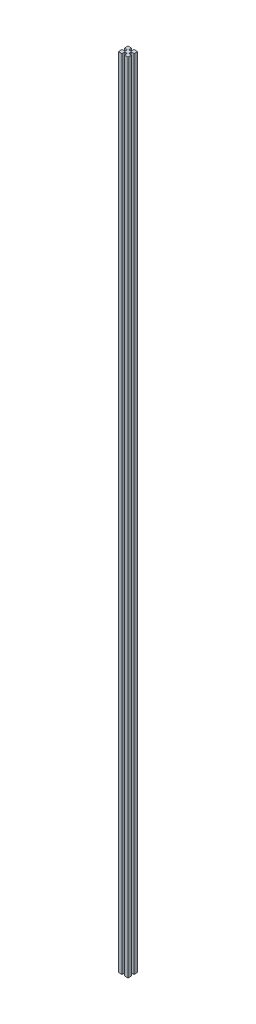
SolidWorks part; units mm, degrees
ref_plane "Front Plane" through (0, 0, 0) normal (0, 0, 1) x (1, 0, 0)
ref_plane "Top Plane" through (0, 0, 0) normal (0, 1, 0) x (1, 0, 0)
ref_plane "Right Plane" through (0, 0, 0) normal (1, 0, 0) x (0, 0, -1)
sketch "Sketch1" plane through (0, 0, 0) normal (0, 1, 0) x (1, 0, 0)
  line L1 (-10, -10) -> (10, -10)
  line L2 (-10, -10) -> (-10, 10)
  line L3 (-10, 10) -> (10, 10)
  line L4 (10, -10) -> (10, 10)
  line L5 (-10, -10) -> (10, 10) construction
  line L6 (-10, 10) -> (10, -10) construction
  point P0 (0, 0)
  dimension "D1" = 20
  dimension "D2" = 20
extrude "Boss-Extrude1" add sketch "Sketch1" along normal blind 825.5 and the other way blind 825.5
sketch "Sketch2" plane through (0, 0, 0) normal (0, 1, 0) x (1, 0, 0)
  line L0 (-2.5, 4) -> (2.5, 4)
  line L1 (-2.5, 4) -> (-2.5, 16)
  line L2 (-2.5, 16) -> (2.5, 16)
  line L3 (2.5, 4) -> (2.5, 16)
  line L4 (-2.5, 4) -> (2.5, 16) construction
  line L5 (-2.5, 16) -> (2.5, 4) construction
  line L6 (4, 2.5) -> (16, 2.5)
  line L7 (4, 2.5) -> (4, -2.5)
  line L8 (4, -2.5) -> (16, -2.5)
  line L9 (16, 2.5) -> (16, -2.5)
  line L10 (4, 2.5) -> (16, -2.5) construction
  line L11 (4, -2.5) -> (16, 2.5) construction
  line L12 (-10, 10) -> (10, -10) construction
  line L13 (-16, 2.5) -> (-4, -2.5) construction
  line L14 (-4, 2.5) -> (-16, -2.5) construction
  line L15 (-4, -2.5) -> (-16, -2.5)
  line L16 (-16, 2.5) -> (-16, -2.5)
  line L17 (-4, 2.5) -> (-16, 2.5)
  line L18 (-4, 2.5) -> (-4, -2.5)
  line L19 (2.5, -4) -> (2.5, -16)
  line L20 (2.5, -4) -> (-2.5, -16) construction
  line L21 (-2.5, -4) -> (2.5, -16) construction
  line L22 (-2.5, -16) -> (2.5, -16)
  line L23 (-2.5, -4) -> (2.5, -4)
  line L24 (-2.5, -4) -> (-2.5, -16)
  line L25 (-10, 10) -> (-10, -10) construction
  line L26 (10, -10) -> (10, 10) construction
  line L27 (-10, -10) -> (10, -10) construction
  line L28 (10, 10) -> (-10, 10) construction
  point P0 (0, 10)
  point P5 (10, 0)
  point P16 (-10, 0)
  point P21 (0, -10)
  dimension "D1" = 5
  dimension "D2" = 12
  dimension "D3" = 5
  dimension "D4" = 12
extrude "Cut-Extrude1" cut sketch "Sketch2" against normal through all both and the other way through all
